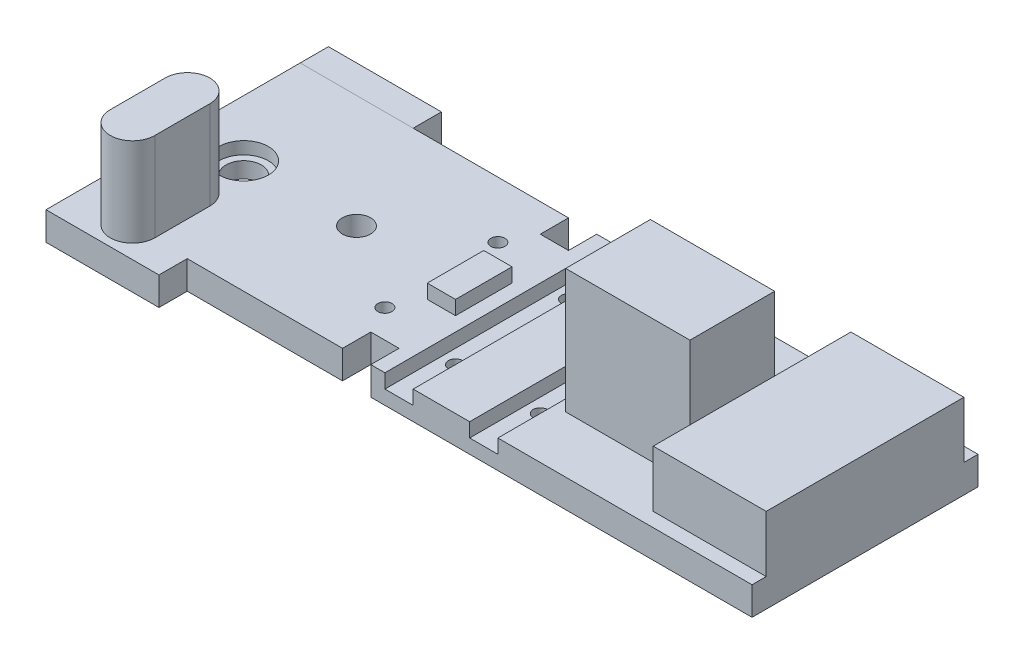
SolidWorks part; units mm, degrees
ref_plane "Front Plane" through (0, 0, 0) normal (0, 0, 1) x (1, 0, 0)
ref_plane "Top Plane" through (0, 0, 0) normal (0, 1, 0) x (1, 0, 0)
ref_plane "Right Plane" through (0, 0, 0) normal (1, 0, 0) x (0, 0, -1)
sketch "Sketch1" plane through (0, 0, 0) normal (0, 1, 0) x (1, 0, 0)
  line L1 (0, 0) -> (304.8, 0)
  line L2 (0, 0) -> (0, 101.6)
  line L3 (0, 101.6) -> (304.8, 101.6)
  line L4 (304.8, 0) -> (304.8, 101.6)
  dimension "D1" = 304.8
  dimension "4" = 101.6
extrude "Boss-Extrude1" add sketch "Sketch1" along normal blind 12.7
sketch "Sketch3" plane through (0, 12.7, 0) normal (0, 1, 0) x (1, 0, 0)
  line L0 (0, 101.6) -> (0, 0) construction
  line L1 (304.8, 101.6) -> (0, 101.6) construction
  circle A0 centre (25.4, 50.8) radius 11.1125
  dimension "D1" = 25.4
  dimension "D3" = 22.225
  dimension "D2" = 50.8
extrude "Cut-Extrude2" cut sketch "Sketch3" against normal blind 5.5562
sketch "Sketch9" plane through (0, 0, 0) normal (0, 0, 1) x (1, 0, 0)
  line L1 (0, 12.7) -> (0, 0) construction
  line L9 (165.1, 25.4) -> (165.1, 0)
  line L10 (0, 0) -> (304.8, 0) construction
  line L19 (0, 12.7) -> (304.8, 12.7) construction
  line L20 (139.7, 12.7) -> (152.4, 12.7)
  line L21 (139.7, 12.7) -> (139.7, 6.35)
  line L22 (139.7, 6.35) -> (152.4, 6.35)
  line L23 (152.4, 12.7) -> (152.4, 6.35)
  line L24 (190.5, 6.35) -> (177.8, 6.35)
  line L25 (177.8, 12.7) -> (177.8, 6.35)
  line L26 (190.5, 12.7) -> (177.8, 12.7)
  line L27 (190.5, 12.7) -> (190.5, 6.35)
  line M17 (304.8, 12.7) -> (0, 12.7)
  dimension "D1" = 12.7
  dimension "D2" = 12.7
  dimension "D3" = 139.7
  dimension "0.25" = 6.35
extrude "Cut-Extrude5" cut sketch "Sketch9" against normal through all contours L23 L21 L22 M17 | L27 L25 L24 M17 region at (184.15, 9.525, 0) region at (146.05, 9.525, 0)
sketch "Sketch15" plane through (0, 6.35, 0) normal (0, 1, 0) x (1, 0, 0)
  line L0 (139.7, 101.6) -> (139.7, 0) construction
  line L3 (177.8, 101.6) -> (177.8, 0) construction
  circle A0 centre (146.05, 25.4) radius 3.175
  circle A1 centre (184.15, 76.2) radius 3.175
  circle A2 centre (184.15, 25.4) radius 3.175
  circle A5 centre (146.05, 76.2) radius 3.175
  circle A6 centre (114.3, 25.4) radius 3.175
  circle A7 centre (114.3, 76.2) radius 3.175
  dimension "D1" = 31.75
  dimension "D7" = 50.8
  dimension "D2" = 31.75
  dimension "D4" = 6.35
  dimension "D5" = 6.35
  dimension "D6" = 6.35
  dimension "D8" = 50.8
  dimension "D9" = 6.35
extrude "Cut-Extrude8" cut sketch "Sketch15" against normal blind 25.4 from surface starting at face at (25.4, 12.7, -39.6875)
sketch "Sketch17" plane through (0, 12.7, 0) normal (0, 1, 0) x (1, 0, 0)
  line L0 (190.5, 0) -> (304.8, 0) construction
  line L1 (195.58, 63.5) -> (251.46, 63.5)
  line L2 (195.58, 63.5) -> (195.58, 25.4)
  line L3 (195.58, 25.4) -> (251.46, 25.4)
  line L4 (251.46, 63.5) -> (251.46, 25.4)
  line L5 (190.5, 101.6) -> (190.5, 0) construction
  dimension "D1" = 38.1
  dimension "D2" = 55.88
  dimension "D3" = 25.4
  dimension "D4" = 5.08
extrude "Boss-Extrude5" add sketch "Sketch17" along normal blind 55.88
sketch "Sketch19" plane through (0, 12.7, 0) normal (0, 1, 0) x (1, 0, 0)
  line L0 (304.8, 0) -> (304.8, 101.6) construction
  line L5 (254, 95.25) -> (304.8, 95.25)
  line L6 (254, 95.25) -> (254, 6.35)
  line L7 (254, 6.35) -> (304.8, 6.35)
  line L8 (304.8, 95.25) -> (304.8, 6.35)
  line L9 (190.5, 0) -> (304.8, 0) construction
  dimension "D3" = 50.8
  dimension "D4" = 88.9
  dimension "D5" = 6.35
extrude "Boss-Extrude6" add sketch "Sketch19" along normal blind 25.4
sketch "Sketch20" plane through (0, 0, 0) normal (-1, 0, 0) x (0, 0, 1)
  line L1 (0, 12.7) -> (12.7, 12.7)
  line L2 (0, 12.7) -> (0, 0)
  line L3 (0, 0) -> (12.7, 0)
  line L4 (12.7, 12.7) -> (12.7, 0)
  line L5 (-101.6, 12.7) -> (-114.3, 12.7)
  line L6 (-101.6, 12.7) -> (-101.6, 0)
  line L7 (-101.6, 0) -> (-114.3, 0)
  line L8 (-114.3, 12.7) -> (-114.3, 0)
  dimension "D1" = 12.7
  dimension "D2" = 12.7
extrude "Boss-Extrude7" add sketch "Sketch20" against normal blind 50.8 separate body
sketch "Sketch21" plane through (0, 7.1437, 0) normal (0, 1, 0) x (1, 0, 0)
  circle A0 centre (25.4, 50.8) radius 7.9375
  dimension "D1" = 15.875
extrude "Cut-Extrude10" cut sketch "Sketch21" against normal through all
sketch "Sketch22" plane through (0, 12.7, 0) normal (0, 1, 0) x (1, 0, 0)
  line L0 (25.4, 25.527) -> (25.4, 0.8077) construction
  line L1 (35.433, 25.527) -> (35.433, 0.8077)
  line L2 (15.367, 25.527) -> (15.367, 0.8077)
  arc A0 (35.433, 25.527) -> (15.367, 25.527) centre (25.4, 25.527) ccw
  arc A1 (15.367, 0.8077) -> (35.433, 0.8077) centre (25.4, 0.8077) ccw
  circle A2 centre (25.4, 50.8) radius 11.1125 construction
  point P3 (25.4, 13.1674)
  point P8 (25.4, 35.56)
  point P11 (25.4, -9.2253)
  dimension "D1" = 15.24
  dimension "D2" = 44.7853
  dimension "D3" = 20.066
extrude "Boss-Extrude8" add sketch "Sketch22" along normal blind 39.878
sketch "Sketch23" plane through (0, 12.7, 0) normal (0, 1, 0) x (1, 0, 0)
  line L0 (50.8, 0) -> (139.7, 0) construction
  circle A0 centre (76.1171, 50.8) radius 6.35
  dimension "D1" = 50.8
extrude "Cut-Extrude11" cut sketch "Sketch23" against normal through all
sketch "Sketch24" plane through (0, 12.7, 0) normal (0, 1, 0) x (1, 0, 0)
  line L1 (120.65, 63.5) -> (133.35, 63.5)
  line L2 (120.65, 63.5) -> (120.65, 38.1)
  line L3 (120.65, 38.1) -> (133.35, 38.1)
  line L4 (133.35, 63.5) -> (133.35, 38.1)
  circle A0 centre (114.3, 25.4) radius 3.175 construction
  dimension "D1" = 25.4
  dimension "D2" = 12.7
  dimension "D3" = 12.7
  dimension "D4" = 6.35
extrude "Boss-Extrude9" add sketch "Sketch24" along normal blind 6.35
sketch "Sketch25" plane through (0, 12.7, 0) normal (0, 1, 0) x (1, 0, 0)
  line L0 (139.7, 101.6) -> (0, 101.6) construction
  line L1 (120.65, 101.6) -> (133.35, 101.6)
  line L2 (120.65, 101.6) -> (120.65, 88.9)
  line L3 (120.65, 88.9) -> (133.35, 88.9)
  line L4 (133.35, 101.6) -> (133.35, 88.9)
  line L5 (50.8, 0) -> (139.7, 0) construction
  line L6 (120.65, 0) -> (133.35, 0)
  line L7 (120.65, 0) -> (120.65, 12.7)
  line L8 (120.65, 12.7) -> (133.35, 12.7)
  line L9 (133.35, 0) -> (133.35, 12.7)
  line L10 (120.65, 63.5) -> (120.65, 38.1) construction
  line L11 (120.65, 63.5) -> (120.65, 38.1) construction
  dimension "D1" = 0
  dimension "D2" = 0
  dimension "D3" = 12.7
  dimension "D4" = 12.7
  dimension "D5" = 12.7
  dimension "D6" = 12.7
extrude "Cut-Extrude12" cut sketch "Sketch25" against normal through all
